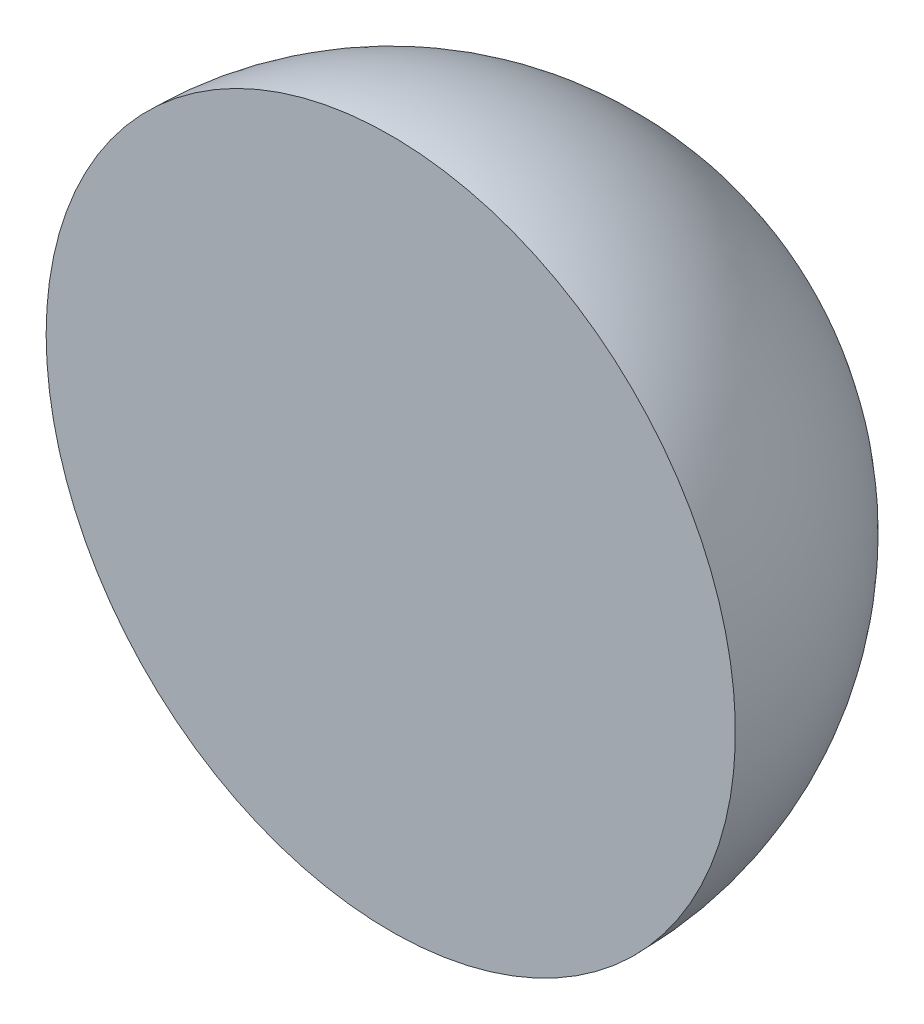
SolidWorks part; units mm, degrees
ref_plane "Front Plane" through (0, 0, 0) normal (0, 0, 1) x (1, 0, 0)
ref_plane "Top Plane" through (0, 0, 0) normal (0, 1, 0) x (1, 0, 0)
ref_plane "Right Plane" through (0, 0, 0) normal (1, 0, 0) x (0, 0, -1)
sketch "Sketch1" plane through (0, 0, 0) normal (0, 0, 1) x (1, 0, 0)
  line L0 (0, -62.5) -> (0, 62.5)
  arc A0 (0, -62.5) -> (0, 62.5) centre (0, 0) ccw
  dimension "D1" = 125
ref_axis "Axis1" through (0, 68.75, 0) along (0, -1, 0)
revolve "Revolve5" add sketch "Sketch1" angle 180 about L0
